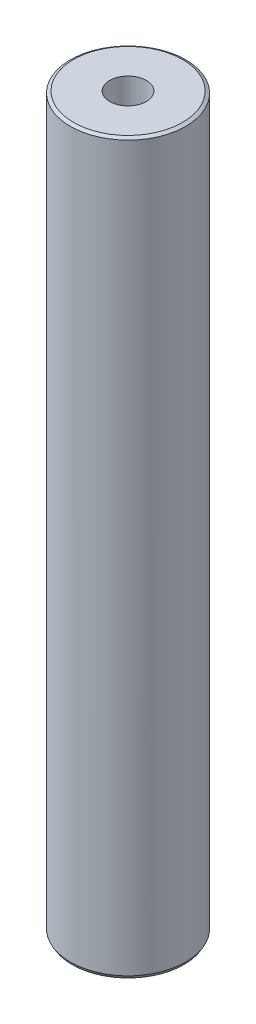
SolidWorks part; units mm, degrees
ref_plane "Front Plane" through (0, 0, 0) normal (0, 0, 1) x (1, 0, 0)
ref_plane "Top Plane" through (0, 0, 0) normal (0, 1, 0) x (1, 0, 0)
ref_plane "Right Plane" through (0, 0, 0) normal (1, 0, 0) x (0, 0, -1)
sketch "Sketch1" plane through (0, 0, 0) normal (0, 1, 0) x (1, 0, 0)
  circle A0 centre (0, 0) radius 47.5
  dimension "SHAFT_OD" = 95
extrude "Boss-Extrude1" add sketch "Sketch1" along normal blind 600
sketch "Sketch2" plane through (0, 0, 0) normal (0, 1, 0) x (1, 0, 0)
  circle A0 centre (0, 0) radius 15.0719
  dimension "BORE_D" = 30.1439
extrude "Cut-Extrude1" cut sketch "Sketch2" along normal through all
chamfer "Chamfer1" distance 1.5005 angle 60 2 edges at (0, 600, 47.5) (0, 0, 47.5) first distance on face at (0, 600, 47.5) first distance on face at (0, 0, 15.0719)
